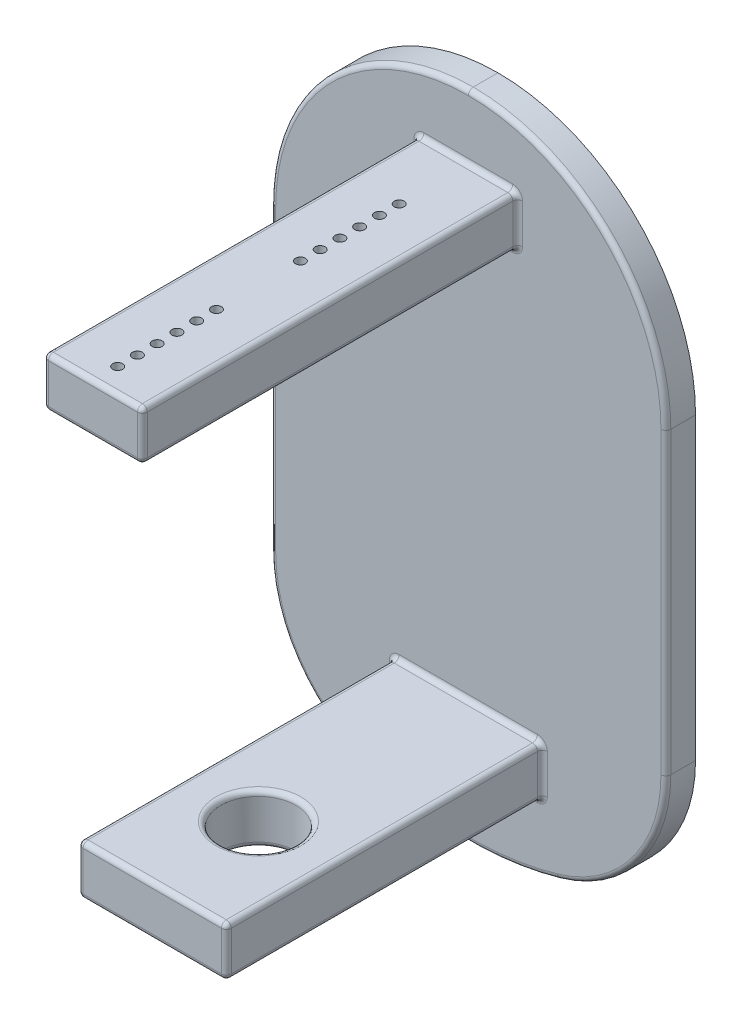
SolidWorks part; units mm, degrees
ref_plane "Front Plane" through (0, 0, 0) normal (0, 0, 1) x (1, 0, 0)
ref_plane "Top Plane" through (0, 0, 0) normal (0, 1, 0) x (1, 0, 0)
ref_plane "Right Plane" through (0, 0, 0) normal (1, 0, 0) x (0, 0, -1)
sketch "Sketch1" plane through (0, 0, 0) normal (0, 0, 1) x (1, 0, 0)
  circle A0 centre (0, 0) radius 33
  dimension "D1" = 66
extrude "Boss-Extrude1" add sketch "Sketch1" along normal blind 3
sketch "Sketch6" plane through (0, 0, 3) normal (0, 0, 1) x (1, 0, 0)
  line L0 (-20, 26.2488) -> (-20, -26.2488)
  line L1 (20, -26.2488) -> (20, 26.2488)
  arc A0 (20, -26.2488) -> (20, 26.2488) centre (0, 0) ccw
  circle A1 centre (0, 0) radius 33
  arc A2 (-20, 26.2488) -> (-20, -26.2488) centre (0, 0) ccw
  dimension "D2" = 20
  dimension "D3" = 40
  dimension "D1" = 0
extrude "Cut-Extrude3" cut sketch "Sketch6" against normal blind 10
fillet "Fillet2" radius 20 2 edges at (-20, 26.2488, 1.5) (20, 26.2488, 1.5)
fillet "Fillet3" radius 15 2 edges at (20, -26.2488, 1.5) (-20, -26.2488, 1.5)
sketch "Sketch2" plane through (0, 0, 3) normal (0, 0, 1) x (1, 0, 0)
  line L1 (-5, 26.5) -> (5, 26.5)
  line L2 (-5, 26.5) -> (-5, 21.5)
  line L3 (-5, 21.5) -> (5, 21.5)
  line L4 (5, 26.5) -> (5, 21.5)
  line L5 (-5, 26.5) -> (5, 21.5) construction
  line L6 (-5, 21.5) -> (5, 26.5) construction
  point P0 (0, 24)
  dimension "D1" = 5
  dimension "D2" = 26.5
  dimension "D3" = 10
extrude "Boss-Extrude2" add sketch "Sketch2" along normal blind 38
sketch "Sketch3" plane through (0, 26.5, 0) normal (0, 1, 0) x (1, 0, 0)
  line L0 (5, -3) -> (-5, -3) construction
  line L1 (5, -41) -> (-5, -41) construction
  circle A0 centre (0, -10) radius 0.5
  circle A1 centre (0, -12) radius 0.5
  circle A2 centre (0, -14) radius 0.5
  circle A3 centre (0, -16) radius 0.5
  circle A4 centre (0, -18) radius 0.5
  circle A5 centre (0, -20) radius 0.5
  circle A6 centre (0, -38.5) radius 0.5
  circle A7 centre (0, -36.5) radius 0.5
  circle A8 centre (0, -34.5) radius 0.5
  circle A9 centre (0, -32.5) radius 0.5
  circle A10 centre (0, -30.5) radius 0.5
  circle A11 centre (0, -28.5) radius 0.5
  point P20 (0, -41)
  dimension "D2" = 1
  dimension "D5" = 8.5
  dimension "D6" = 2
  dimension "D1" = 7
  dimension "D7" = 2
  dimension "D3" = 6
  dimension "D4" = 6
extrude "Cut-Extrude1" cut sketch "Sketch3" against normal blind 5
sketch "Sketch4" plane through (0, 0, 3) normal (0, 0, 1) x (1, 0, 0)
  line L1 (-7.5, -20.5) -> (7.5, -20.5)
  line L2 (-7.5, -20.5) -> (-7.5, -25.5)
  line L3 (-7.5, -25.5) -> (7.5, -25.5)
  line L4 (7.5, -20.5) -> (7.5, -25.5)
  line L5 (-7.5, -20.5) -> (7.5, -25.5) construction
  line L6 (-7.5, -25.5) -> (7.5, -20.5) construction
  line L7 (-5, 21.5) -> (5, 21.5) construction
  point P0 (0, -23)
  dimension "D1" = 42
  dimension "D2" = 15
  dimension "D3" = 5
extrude "Boss-Extrude3" add sketch "Sketch4" along normal blind 32
sketch "Sketch5" plane through (0, -20.5, 0) normal (0, 1, 0) x (1, 0, 0)
  line L0 (-7.5, -3) -> (7.5, -3) construction
  circle A0 centre (0, -24.25) radius 3.8
  dimension "D1" = 21.25
  dimension "D2" = 7.6
extrude "Cut-Extrude2" cut sketch "Sketch5" against normal blind 28
fillet "Fillet4" radius 0.5 33 edges at (7.5, -20.5, 19) (0, -20.5, 35) (-7.5, -20.5, 19) (0, -20.5, 28.05) (-7.5, -25.5, 19) (0, -25.5, 35) (7.5, -25.5, 19) (0, -25.5, 28.05) (5, 21.5, 22) (-5, 21.5, 22) (0, 21.5, 41) (5, 26.5, 22) (0, 26.5, 41) (-5, 26.5, 22) (-7.5, -23, 3) (0, -25.5, 3) (7.5, -23, 3) (0, -20.5, 3) (-5, 24, 3) (0, 21.5, 3) (5, 24, 3) (0, 26.5, 3) (-16.9896, -26.3055, 3) (-20, -2.1458, 3) (-14.1421, 27.1421, 3) (14.1421, 27.1421, 3) (20, -2.1458, 3) (16.9896, -26.3055, 3) (0, -33, 3) (-7.5, -23, 35) (7.5, -23, 35) (-5, 24, 41) (5, 24, 41)
